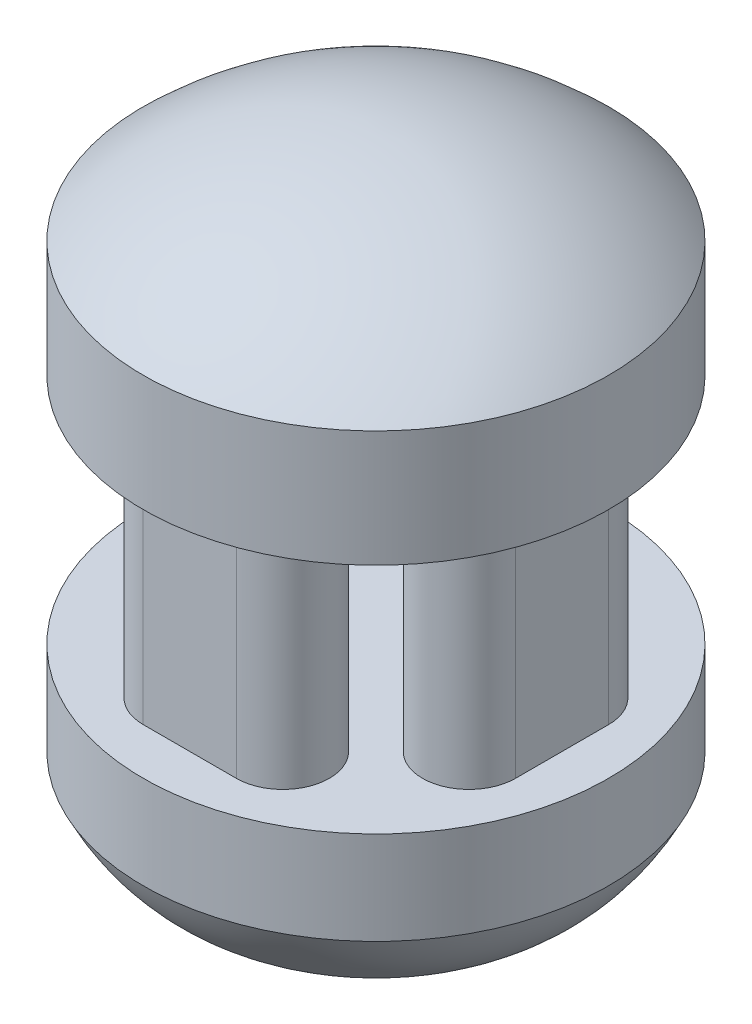
SolidWorks part; units mm, degrees
ref_plane "Front Plane" through (0, 0, 0) normal (0, 0, 1) x (1, 0, 0)
ref_plane "Top Plane" through (0, 0, 0) normal (0, 1, 0) x (1, 0, 0)
ref_plane "Right Plane" through (0, 0, 0) normal (1, 0, 0) x (0, 0, -1)
sketch "Sketch1" plane through (0, 0, 0) normal (0, 0, 1) x (1, 0, 0)
  line L0 (0, 0) -> (0, 3.175)
  line L1 (0, 3.175) -> (-6.35, 3.175)
  line L2 (-6.35, 3.175) -> (-6.35, 0)
  line L3 (-6.35, 0) -> (0, 0)
  dimension "D1" = 3.175
  dimension "D2" = 6.35
revolve "button top" add sketch "Sketch1" angle 360 about L0
dome "domey top" faces to dome 1 distance 2.54 reverse direction no elliptical dome no face at (0, 3.175, -6.35) parameters "D1"=2.54
ref_axis "button central axis" through (0, 3.175, 0) along (0, -1, 0)
sketch "Sketch2" plane through (0, 0, 0) normal (0, -1, 0) x (1, 0, 0)
  line L0 (-1.27, -3.81) -> (1.27, -3.81) construction
  line L1 (-1.27, -2.54) -> (1.27, -2.54)
  line L2 (-1.27, -5.08) -> (1.27, -5.08)
  arc A0 (-1.27, -2.54) -> (-1.27, -5.08) centre (-1.27, -3.81) ccw
  arc A1 (1.27, -5.08) -> (1.27, -2.54) centre (1.27, -3.81) ccw
  point P2 (0, -3.81)
  dimension "D3" = 1.27
  dimension "D1" = 3.81
  dimension "D2" = 2.54
extrude "one leg" add sketch "Sketch2" along normal blind 6.35
pattern_circular "all legs" count 4 over 360 about axis through (0, 3.175, 0) along (0, -1, 0) of "one leg"
sketch "Sketch3" plane through (0, -6.35, 0) normal (0, -1, 0) x (1, 0, 0)
  circle A0 centre (0, 0) radius 6.35
  dimension "D1" = 12.7
extrude "base" add sketch "Sketch3" along normal blind 2.54
sketch "Sketch5" plane through (0, -6.35, 0) normal (0, 1, 0) x (1, 0, 0)
  circle A0 centre (0, 0) radius 0.635
sketch "Sketch6" plane through (0, 0, 0) normal (1, 0, 0) x (0, 0, -1)
  line L0 (0, -8.89) -> (0, -11.938)
  line L1 (-6.35, -8.89) -> (6.35, -8.89) construction
  line L2 (0, -8.89) -> (6.35, -8.89)
  spline S0 degree 3 poles (0, -11.938) (2.9633, -11.938) (5.0382, -11.5542) (6.35, -8.89) knots 0 0 0 0 1 1 1 1
revolve "Revolve2" add sketch "Sketch6" angle 360 about L0
